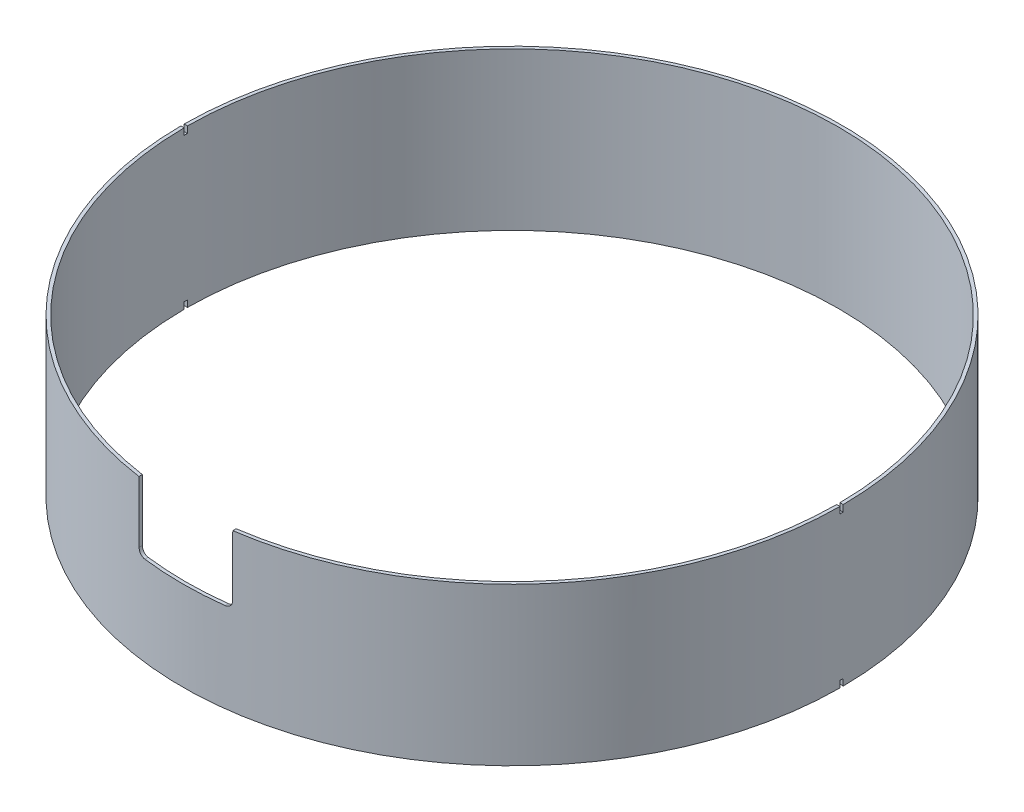
SolidWorks part; units mm, degrees
ref_plane "Front Plane" through (0, 0, 0) normal (0, 0, 1) x (1, 0, 0)
ref_plane "Top Plane" through (0, 0, 0) normal (0, 1, 0) x (1, 0, 0)
ref_plane "Right Plane" through (0, 0, 0) normal (1, 0, 0) x (0, 0, -1)
sketch "Эскиз1" plane through (0, 0, 0) normal (0, 1, 0) x (1, 0, 0)
  circle A0 centre (0, 0) radius 50.3
  circle A1 centre (0, 0) radius 49.8
extrude "Бобышка-Вытянуть1" add sketch "Эскиз1" along normal blind 24
sketch "Эскиз2" plane through (0, 0, 0) normal (0, 0, 1) x (1, 0, 0)
  line L0 (-7.1302, 13.65) -> (-7.1588, 24)
  line L1 (7.1588, 24) -> (7.1302, 13.65)
  line L2 (7.1302, 13.65) -> (-7.1302, 13.65)
  line L3 (-7.1588, 24) -> (7.1588, 24)
  line L4 (49.8, 24) -> (-49.8, 24) construction
  point P4 (0, 24)
extrude "Вырез-Вытянуть1" cut sketch "Эскиз2" along normal blind 52
sketch "Эскиз3" plane through (0, 0, 0) normal (1, 0, 0) x (0, 0, -1)
  line L0 (0, 24) -> (0.25, 24)
  line L8 (0, 24) -> (-0.25, 24)
  line L9 (-0.25, 24) -> (-0.25, 23)
  line L10 (-0.25, 23) -> (0.25, 23)
  line L11 (0.25, 23) -> (0.25, 24)
  line L12 (0, 0) -> (0, 24) construction
  line L14 (0, 12) -> (3.0275, 12) construction
  line L15 (0.25, 1) -> (0.25, 0)
  line L16 (-0.25, 1) -> (0.25, 1)
  line L17 (-0.25, 0) -> (-0.25, 1)
  line L18 (0, 0) -> (-0.25, 0)
  line L19 (0, 0) -> (0.25, 0)
extrude "Вырез-Вытянуть2" cut sketch "Эскиз3" against normal blind 52 and the other way blind 52
fillet "Скругление1" radius 1 2 edges at (7.1302, 13.65, 49.5395) (-7.1302, 13.65, 49.5395)
